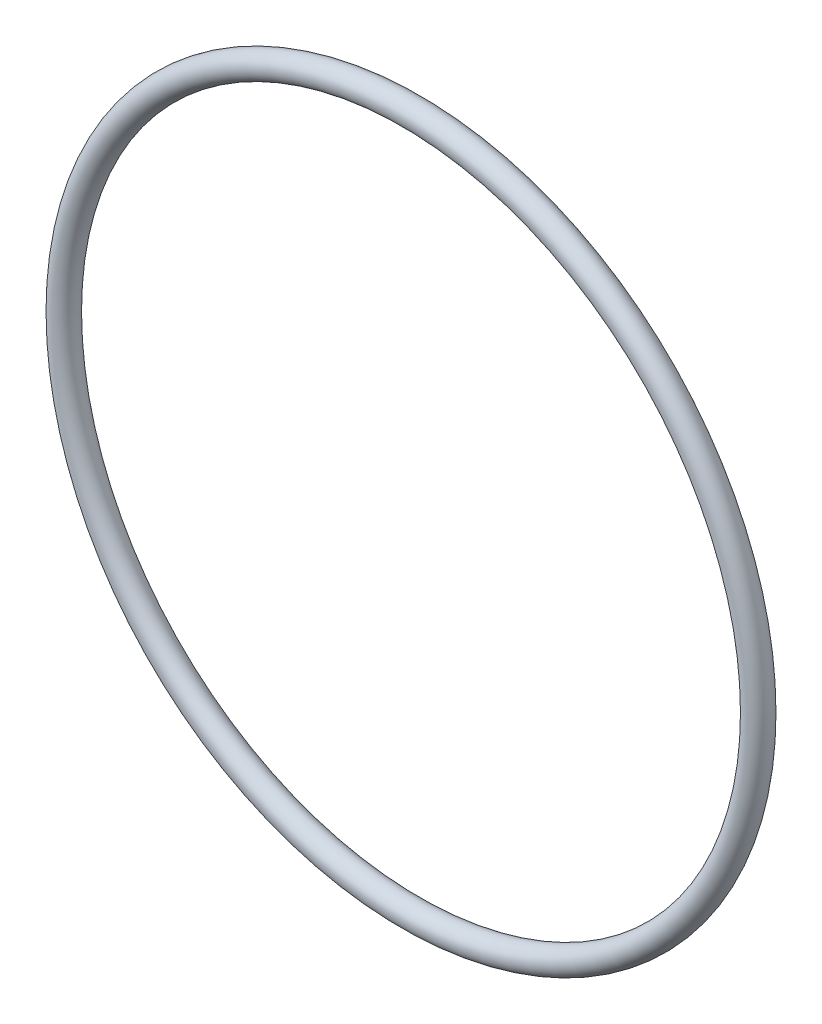
SolidWorks part; units mm, degrees
ref_plane "Front" through (0, 0, 0) normal (0, 0, 1) x (1, 0, 0)
ref_plane "Top" through (0, 0, 0) normal (0, 1, 0) x (1, 0, 0)
ref_plane "Right" through (0, 0, 0) normal (1, 0, 0) x (0, 0, -1)
sketch "Sketch1" plane through (0, 0, 0) normal (1, 0, 0) x (0, -1, 0)
  line L0 (0, -0.889) -> (0, 0.889) construction
  line L2 (-27.9959, 0) -> (27.9959, 0) construction
  line L3 (-23.6728, 0) -> (23.6728, 0) construction
  circle A0 centre (24.5618, 0) radius 0.889
  point P9 (23.6728, 0)
  point P10 (25.4508, 0)
  point P13 (24.5618, 0.889)
  point P14 (24.5618, -0.889)
  dimension "Width" = 1.778
  dimension "ID" = 47.3456
revolve "Revolve1" add sketch "Sketch1" angle 360 about L0
ref_axis "Axis1" through (0, 0, -0.9779) along (0, 0, 1)
